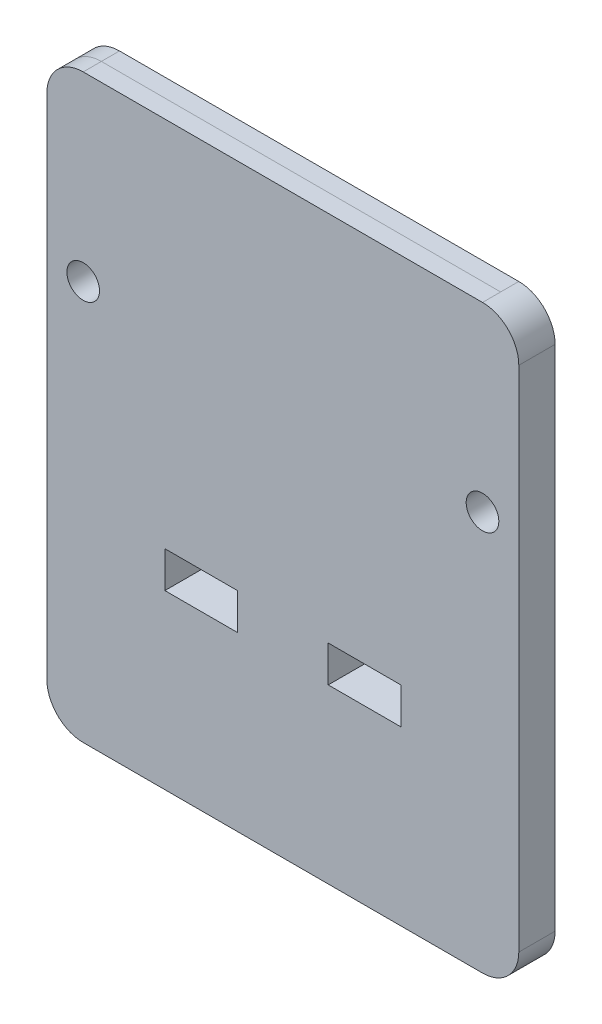
SolidWorks part; units mm, degrees
material "Pink Foam"
ref_plane "Front Plane" through (0, 0, 0) normal (0, 0, 1) x (1, 0, 0)
ref_plane "Top Plane" through (0, 0, 0) normal (0, 1, 0) x (1, 0, 0)
ref_plane "Right Plane" through (0, 0, 0) normal (1, 0, 0) x (0, 0, -1)
sketch "Sketch1" plane through (0, 0, 0) normal (0, 0, 1) x (1, 0, 0)
  line L1 (-139.7, -203.2) -> (139.7, -203.2)
  line L2 (-165.1, -177.8) -> (-165.1, 177.8)
  line L3 (-139.7, 203.2) -> (139.7, 203.2)
  line L4 (165.1, -177.8) -> (165.1, 177.8)
  line L5 (-165.1, -203.2) -> (165.1, 203.2) construction
  line L6 (-165.1, 203.2) -> (165.1, -203.2) construction
  line L7 (-133.3733, -107.95) -> (133.3733, -107.95) construction
  line L8 (-158.7733, -82.55) -> (-158.7733, 82.55) construction
  line L9 (-133.3733, 107.95) -> (133.3733, 107.95) construction
  line L10 (158.7733, -82.55) -> (158.7733, 82.55) construction
  line L11 (-158.7733, -107.95) -> (158.7733, 107.95) construction
  line L12 (-158.7733, 107.95) -> (158.7733, -107.95) construction
  arc A0 (-139.7, -203.2) -> (-165.1, -177.8) centre (-139.7, -177.8) cw
  arc A1 (139.7, -203.2) -> (165.1, -177.8) centre (139.7, -177.8) ccw
  arc A2 (139.7, 203.2) -> (165.1, 177.8) centre (139.7, 177.8) cw
  arc A3 (-165.1, 177.8) -> (-139.7, 203.2) centre (-139.7, 177.8) cw
  circle A4 centre (-139.7, 76.2) radius 11.422
  circle A5 centre (139.7, 76.2) radius 11.422
  arc A6 (-133.3733, -107.95) -> (-158.7733, -82.55) centre (-133.3733, -82.55) cw construction
  arc A7 (133.3733, -107.95) -> (158.7733, -82.55) centre (133.3733, -82.55) ccw construction
  arc A8 (133.3733, 107.95) -> (158.7733, 82.55) centre (133.3733, 82.55) cw construction
  arc A9 (-158.7733, 82.55) -> (-133.3733, 107.95) centre (-133.3733, 82.55) cw construction
  point P0 (0, 0)
  point P23 (0, 0)
  dimension "D3" = 25.4
  dimension "D7" = 22.844
  dimension "D8" = 317.5465
  dimension "D10" = 25.4
  dimension "D1" = 330.2
  dimension "D2" = 406.4
  dimension "D4" = 25.4
  dimension "D5" = 127
  dimension "D6" = 25.4
  dimension "D9" = 215.9
extrude "Boss-Extrude1" add sketch "Sketch1" along normal blind 25.4
ref_plane "Plane1" through (0, 0, 12.7) normal (0, 0, 1) x (1, 0, 0)
sketch "Sketch2" plane through (0, 0, 0) normal (0, 0, -1) x (-1, 0, 0)
  line L8 (-82.55, -82.55) -> (-31.75, -82.55)
  line L9 (-31.75, -82.55) -> (-31.75, -57.15)
  line L10 (-31.75, -57.15) -> (-82.55, -57.15)
  line L11 (-82.55, -57.15) -> (-82.55, -82.55)
  line L16 (31.75, -82.55) -> (82.55, -82.55)
  line L17 (31.75, -57.15) -> (31.75, -82.55)
  line L18 (82.55, -57.15) -> (31.75, -57.15)
  line L19 (82.55, -82.55) -> (82.55, -57.15)
  dimension "D1" = 31.75
  dimension "D2" = 82.55
  dimension "D3" = 31.75
  dimension "D4" = 57.15
  dimension "D5" = 82.55
extrude "Foam Insert Cut-Throughs" cut sketch "Sketch2" against normal blind 25.4
split line "Split Line1"
